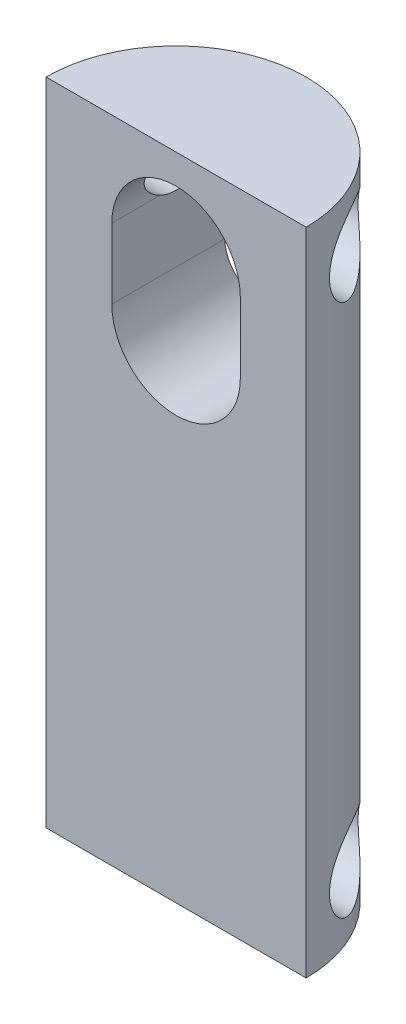
SolidWorks part; units mm, degrees
ref_plane "Front Plane" through (0, 0, 0) normal (0, 0, 1) x (1, 0, 0)
ref_plane "Top Plane" through (0, 0, 0) normal (0, 1, 0) x (1, 0, 0)
ref_plane "Right Plane" through (0, 0, 0) normal (1, 0, 0) x (0, 0, -1)
sketch "Sketch1" plane through (0, 0, 0) normal (0, 1, 0) x (1, 0, 0)
  line L1 (-10, 5) -> (10, 5)
  line L2 (-10, 5) -> (-10, -5)
  line L3 (-10, -5) -> (10, -5)
  line L4 (10, 5) -> (10, -5)
  line L5 (-10, 5) -> (10, -5) construction
  line L6 (-10, -5) -> (10, 5) construction
  point P0 (0, 0)
  dimension "D1" = 20
  dimension "D2" = 10
extrude "Boss-Extrude1" add sketch "Sketch1" along normal blind 50
sketch "Sketch2" plane through (10, 0, 0) normal (1, 0, 0) x (0, 0, -1)
  circle A0 centre (0, 4.5098) radius 3
  dimension "D1" = 6
extrude "Cut-Extrude1" cut sketch "Sketch2" against normal through all
sketch "Sketch3" plane through (0, 0, -5) normal (0, 0, -1) x (-1, 0, 0)
  line L0 (0, 37.4047) -> (0, 42.7951) construction
  line L1 (-4.9412, 37.4047) -> (-4.9412, 42.7951)
  line L2 (4.9412, 37.4047) -> (4.9412, 42.7951)
  arc A0 (-4.9412, 37.4047) -> (4.9412, 37.4047) centre (0, 37.4047) ccw
  arc A1 (4.9412, 42.7951) -> (-4.9412, 42.7951) centre (0, 42.7951) ccw
  point P3 (0, 40.0999)
  point P8 (4.9412, 37.4047)
  point P9 (0, 40.0999)
extrude "Cut-Extrude2" cut sketch "Sketch3" against normal blind 14
pattern_linear "LPattern1" count 2 spacing 41 along (0, 1, 0) of "Cut-Extrude1"
fillet "Fillet1" radius 10 2 edges at (-10, 25, -5) (10, 25, -5)
